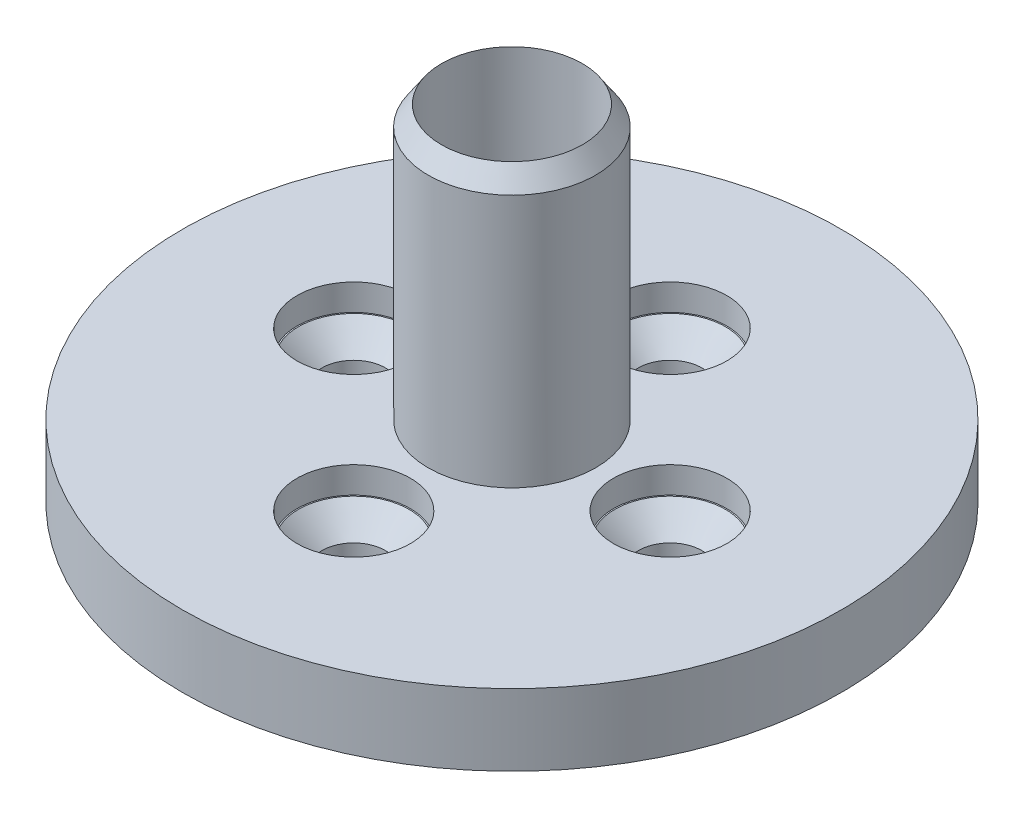
SolidWorks part; units mm, degrees
ref_plane "Front Plane" through (0, 0, 0) normal (0, 0, 1) x (1, 0, 0)
ref_plane "Top Plane" through (0, 0, 0) normal (0, 1, 0) x (1, 0, 0)
ref_plane "Right Plane" through (0, 0, 0) normal (1, 0, 0) x (0, 0, -1)
ref_axis "Axis1" through (-6.6339, 0, 0) along (1, 0, 0)
sketch "Sketch1" plane through (0, 0, 0) normal (0, 1, 0) x (1, 0, 0)
  circle A0 centre (0, 0) radius 12.5
  circle A1 centre (0, 0) radius 6 construction
  circle A2 centre (6, 0) radius 1.2
  circle A3 centre (0, 6) radius 1.2
  circle A4 centre (-6, 0) radius 1.2
  circle A5 centre (0, -6) radius 1.2
  circle A6 centre (0, 0) radius 2.3713
  point P14 (0, 0)
  dimension "D1" = 25
  dimension "D2" = 12
  dimension "D3" = 2.4
  dimension "D5" = 4.7425
  dimension "D4" = 4
extrude "Boss-Extrude1" add sketch "Sketch1" along normal blind 2.715 contours A0 A6 A5 A4 A3 A2 region at (-12.1464, 0, 0)
sketch "Sketch2" plane through (0, 2.715, 0) normal (0, 1, 0) x (1, 0, 0)
  circle A0 centre (0, 6) radius 2.15
  circle A1 centre (-6, 0) radius 2.15
  circle A2 centre (6, 0) radius 2.15
  circle A3 centre (0, -6) radius 2.15
  circle A4 centre (0, 0) radius 3.175
  dimension "D1" = 4.3
  dimension "D2" = 6.35
extrude "Cut-Extrude1" cut sketch "Sketch2" against normal blind 1
chamfer "Chamfer1" distance 0.9 angle 45 5 edges at (0, 1.715, 7.2) (6, 1.715, 1.2) (0, 1.715, 2.3713) (-6, 1.715, 1.2) (0, 1.715, -4.8)
sketch "Sketch3" plane through (0, 0, 0) normal (0, -1, 0) x (1, 0, 0)
  circle A0 centre (0, 0) radius 3.175 construction
  circle A1 centre (0, 0) radius 2.3713 construction
  circle A2 centre (0, 0) radius 3.175
  circle A3 centre (0, 0) radius 2.3713
extrude "Boss-Extrude2" add sketch "Sketch3" against normal blind 13.81
sketch "Sketch4" plane through (0, 13.81, 0) normal (0, 1, 0) x (1, 0, 0)
  circle A0 centre (0, 0) radius 2.3713 construction
  circle A1 centre (0, 0) radius 2.3713
  circle A2 centre (0, 0) radius 2.6713
  dimension "D1" = 0.3
extrude "Cut-Extrude2" cut sketch "Sketch4" against normal blind 13.81
chamfer "Chamfer2" distance 1 angle 56 1 edges at (0, 13.81, -3.175) first distance on face at (0, 13.81, 2.6713)
